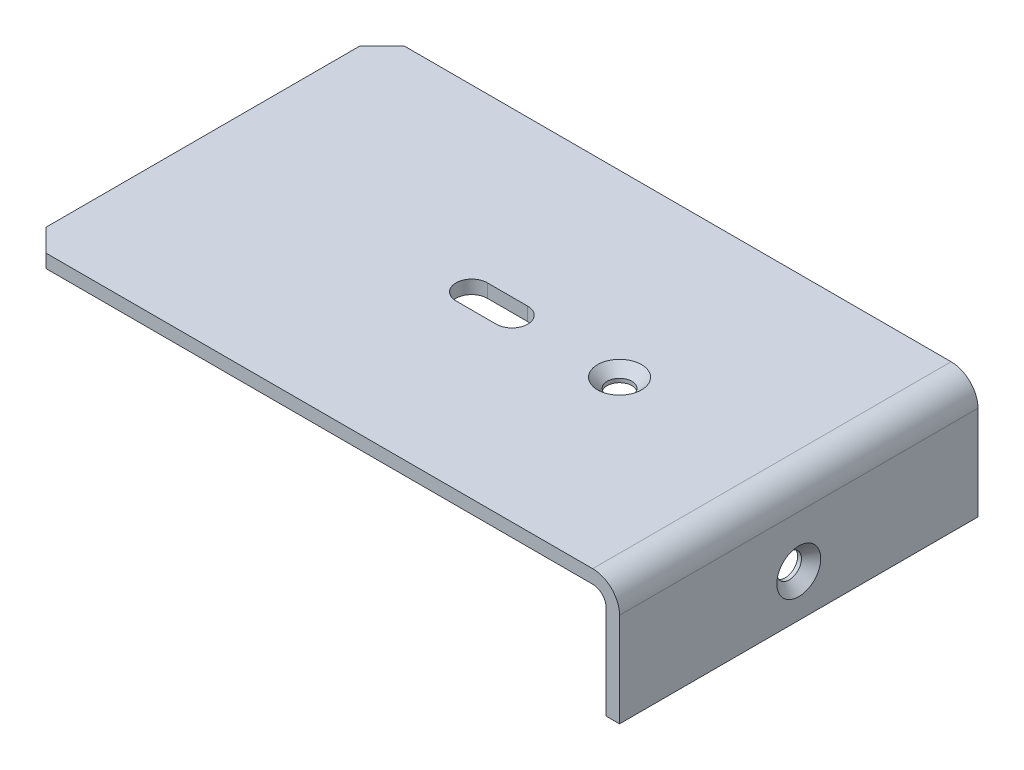
SolidWorks part; units mm, degrees
ref_plane "face" through (0, 0, 0) normal (0, 0, 1) x (1, 0, 0)
ref_plane "dessus" through (0, 0, 0) normal (0, 1, 0) x (1, 0, 0)
ref_plane "droite" through (0, 0, 0) normal (1, 0, 0) x (0, 0, -1)
sketch "Esquisse1" plane through (0, 0, 0) normal (0, 0, 1) x (1, 0, 0)
  line L0 (-3, 0) -> (-130, 0)
  line L1 (0, -3) -> (0, -24)
  arc A0 (0, -3) -> (-3, 0) centre (-3, -3) ccw
  point P6 (0, 0)
  dimension "D3" = 3
  dimension "D1" = 130
  dimension "D2" = 24
extrude "Base-Extru.-Mince" add sketch "Esquisse1" along normal mid plane 80 thin thin type one direction reverse wall 3
chamfer "Chanfrein1" distance 5 angle 45 2 edges at (-130, 1.5, -40) (-130, 1.5, 40)
sketch "Esquisse3" plane through (0, 3, 0) normal (0, 1, 0) x (-1, 0, 0)
  line L0 (130, 0) -> (30, 0) construction
  line L1 (130, 35) -> (130, -35) construction
  line L2 (70, 20) -> (70, -20) construction
  line L3 (61, 20) -> (61, -10) construction
  line L4 (70, 3.5) -> (61, 3.5)
  line L5 (70, -3.5) -> (61, -3.5)
  line L6 (37, 10) -> (37, -10) construction
  line L7 (0, 40) -> (0, -40) construction
  arc A0 (70, -3.5) -> (70, 3.5) centre (70, 0) ccw
  arc A1 (61, 3.5) -> (61, -3.5) centre (61, 0) ccw
  circle A2 centre (37, 0) radius 2.75
  dimension "D3" = 7
  dimension "D4" = 7
  dimension "D6" = 5.5
  dimension "D1" = 61
  dimension "D2" = 70
  dimension "D7" = 37
extrude "Enlèv. mat.-Extru.1" cut sketch "Esquisse3" against normal through all
sketch "Esquisse4" plane through (3, 0, 0) normal (1, 0, 0) x (0, 0, -1)
  line L0 (0, -24.425) -> (0, -7.2998) construction
  line L1 (0, 0) -> (0, 3) construction
  line L2 (-40, 3) -> (40, 3) construction
  circle A0 centre (0, -14.5) radius 2.75
  dimension "D2" = 5.5
  dimension "D1" = 17.5
extrude "Enlèv. mat.-Extru.2" cut sketch "Esquisse4" against normal through all
chamfer "Chanfrein2" distance 2.15 angle 45 2 edges at (-39.75, 3, 0) (3, -11.75, 0)
ref_axis "Axe1" through (0, -14.5, 0) along (1, 0, 0)
